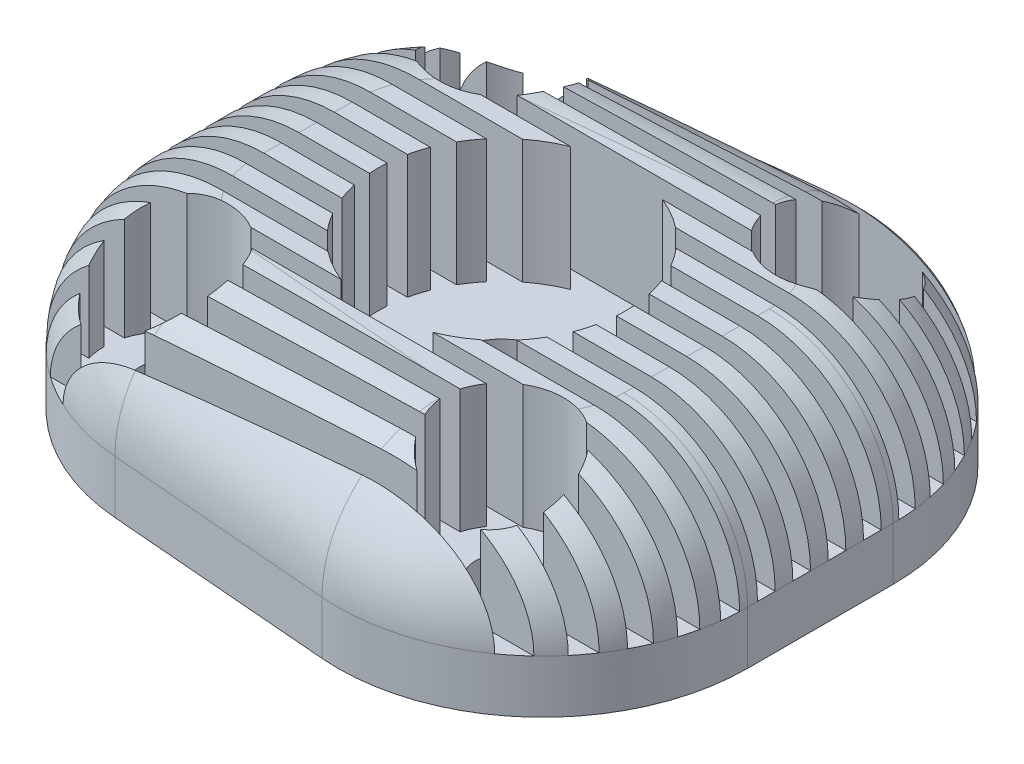
SolidWorks part; units mm, degrees
material "Alloy Steel"
ref_plane "Front Plane" through (0, 0, 0) normal (0, 0, 1) x (1, 0, 0)
ref_plane "Top Plane" through (0, 0, 0) normal (0, 1, 0) x (1, 0, 0)
ref_plane "Right Plane" through (0, 0, 0) normal (1, 0, 0) x (0, 0, -1)
sketch "Sketch1" plane through (0, 0, 0) normal (0, 1, 0) x (1, 0, 0)
  line L0 (5.2212, 15.708) -> (-7.5303, 14.4316)
  line L1 (-17.9681, 2.8969) -> (-17.9681, -3.0145)
  line L2 (-7.3192, -14.5684) -> (5.4324, -15.6096)
  line L3 (17.9681, -4.0557) -> (17.9681, 4.1733)
  line L4 (-17.9681, -0.0588) -> (17.9681, 0.0588) construction
  arc A0 (-7.5303, 14.4316) -> (-17.9681, 2.8969) centre (-6.3758, 2.8969) ccw
  arc A1 (-17.9681, -3.0145) -> (-7.3192, -14.5684) centre (-6.3758, -3.0145) ccw
  arc A2 (5.4324, -15.6096) -> (17.9681, -4.0557) centre (6.3758, -4.0557) ccw
  arc A3 (17.9681, 4.1733) -> (5.2212, 15.708) centre (6.3758, 4.1733) ccw
  point P14 (0, 0)
  dimension "D1" = 29
extrude "Boss-Extrude1" add sketch "Sketch1" along normal blind 10
sketch "Sketch3" plane through (0, 0, 0) normal (0, -1, 0) x (1, 0, 0)
  line L0 (-15.9681, 3.0145) -> (-15.9681, -2.8969)
  line L1 (-7.3311, -12.4416) -> (5.4204, -13.7179)
  line L2 (15.9681, -4.1733) -> (15.9681, 4.0557)
  line L3 (5.5951, 13.6162) -> (-7.1564, 12.575)
  line L4 (17.9681, -4.1733) -> (17.9681, 4.0557)
  line L5 (5.4324, 15.6096) -> (-7.3192, 14.5684)
  line L6 (-17.9681, 3.0145) -> (-17.9681, -2.8969)
  line L7 (-7.5303, -14.4316) -> (5.2212, -15.708)
  line L8 (17.9681, -4.1733) -> (17.9681, 4.0557) construction
  line L9 (5.4324, 15.6096) -> (-7.3192, 14.5684) construction
  line L10 (-17.9681, 3.0145) -> (-17.9681, -2.8969) construction
  line L11 (-7.5303, -14.4316) -> (5.2212, -15.708) construction
  arc A0 (-7.1564, 12.575) -> (-15.9681, 3.0145) centre (-6.3758, 3.0145) ccw
  arc A1 (-15.9681, -2.8969) -> (-7.3311, -12.4416) centre (-6.3758, -2.8969) ccw
  arc A2 (5.4204, -13.7179) -> (15.9681, -4.1733) centre (6.3758, -4.1733) ccw
  arc A3 (15.9681, 4.0557) -> (5.5951, 13.6162) centre (6.3758, 4.0557) ccw
  arc A4 (5.2212, -15.708) -> (17.9681, -4.1733) centre (6.3758, -4.1733) ccw
  arc A5 (17.9681, 4.0557) -> (5.4324, 15.6096) centre (6.3758, 4.0557) ccw
  arc A6 (-7.3192, 14.5684) -> (-17.9681, 3.0145) centre (-6.3758, 3.0145) ccw
  arc A7 (-17.9681, -2.8969) -> (-7.5303, -14.4316) centre (-6.3758, -2.8969) ccw
  arc A8 (5.2212, -15.708) -> (17.9681, -4.1733) centre (6.3758, -4.1733) ccw construction
  arc A9 (17.9681, 4.0557) -> (5.4324, 15.6096) centre (6.3758, 4.0557) ccw construction
  arc A10 (-7.3192, 14.5684) -> (-17.9681, 3.0145) centre (-6.3758, 3.0145) ccw construction
  arc A11 (-17.9681, -2.8969) -> (-7.5303, -14.4316) centre (-6.3758, -2.8969) ccw construction
  dimension "D1" = 0
  dimension "D2" = 2
extrude "Boss-Extrude2" add sketch "Sketch3" along normal blind 0.5
sketch "Sketch4" plane through (0, -0.5, 0) normal (0, -1, 0) x (1, 0, 0)
  circle A0 centre (0, 0) radius 10.5
  dimension "D1" = 21
extrude "Boss-Extrude3" add sketch "Sketch4" along normal blind 3.5
sketch "Sketch5" plane through (0, -4, 0) normal (0, -1, 0) x (1, 0, 0)
  circle A0 centre (0, 0) radius 3
  dimension "D1" = 6
sketch "Sketch7" plane through (0, 10, 0) normal (0, 1, 0) x (1, 0, 0)
  line L1 (9.5, -9.5) -> (-9.5, -9.5) construction
  line L2 (9.5, -9.5) -> (9.5, 9.5) construction
  line L3 (9.5, 9.5) -> (-9.5, 9.5) construction
  line L4 (-9.5, -9.5) -> (-9.5, 9.5) construction
  line L5 (9.5, -9.5) -> (-9.5, 9.5) construction
  line L6 (9.5, 9.5) -> (-9.5, -9.5) construction
  circle A0 centre (0, 0) radius 7
  dimension "D1" = 14
  dimension "D2" = 19
  dimension "D3" = 19
sketch "Sketch8" plane through (0, 10, 0) normal (0, 1, 0) x (1, 0, 0)
  line L1 (9.5, -9.5) -> (-9.5, -9.5) construction
  line L2 (9.5, -9.5) -> (9.5, 9.5) construction
  line L3 (9.5, 9.5) -> (-9.5, 9.5) construction
  line L4 (-9.5, -9.5) -> (-9.5, 9.5) construction
  circle A0 centre (-9.5, 9.5) radius 1.5
  circle A1 centre (9.5, 9.5) radius 1.5
  circle A2 centre (9.5, -9.5) radius 1.5
  circle A3 centre (-9.5, -9.5) radius 1.5
  dimension "D5" = 3
  dimension "D1" = 19
  dimension "D2" = 19
  dimension "D3" = 9.5
  dimension "D4" = 9.5
fillet "Fillet2" radius 7 8 edges at (-17.9681, 10, 0.0588) (-14.9713, 10, -10.675) (-1.1546, 10, -15.0698) (14.1539, 10, -12.7688) (17.9681, 10, -0.0588) (14.2322, 10, 12.5798) (-0.9434, 10, 15.089) (-14.8998, 10, 10.8709)
sketch "Sketch10" plane through (17.9681, 0, 0) normal (1, 0, 0) x (0, 0, -1)
  line L0 (-13.5, 3) -> (-13.5, 11)
  line L2 (-4.0557, 3) -> (-15.648, 3) construction
  line L3 (-13.5, 11) -> (-12.5, 11)
  line L4 (0, 0) -> (0, 15.1807) construction
  line L5 (-13.5, 3) -> (-12.5, 3)
  line L6 (-12.5, 3) -> (-12.5, 11)
  line L7 (-10.5, 3) -> (-10.5, 11)
  line L8 (-11.5, 3) -> (-11.5, 11)
  line L9 (-11.5, 11) -> (-10.5, 11)
  line L10 (-11.5, 3) -> (-10.5, 3)
  line L11 (-8.5, 3) -> (-8.5, 11)
  line L12 (-9.5, 3) -> (-9.5, 11)
  line L13 (-9.5, 11) -> (-8.5, 11)
  line L14 (-9.5, 3) -> (-8.5, 3)
  line L15 (-6.5, 3) -> (-6.5, 11)
  line L16 (-7.5, 3) -> (-7.5, 11)
  line L17 (-7.5, 11) -> (-6.5, 11)
  line L18 (-7.5, 3) -> (-6.5, 3)
  line L19 (-4.5, 3) -> (-4.5, 11)
  line L20 (-5.5, 3) -> (-5.5, 11)
  line L21 (-5.5, 11) -> (-4.5, 11)
  line L22 (-5.5, 3) -> (-4.5, 3)
  line L23 (-2.5, 3) -> (-2.5, 11)
  line L24 (-3.5, 3) -> (-3.5, 11)
  line L25 (-3.5, 11) -> (-2.5, 11)
  line L26 (-3.5, 3) -> (-2.5, 3)
  line L27 (-0.5, 3) -> (-0.5, 11)
  line L28 (-1.5, 3) -> (-1.5, 11)
  line L29 (-1.5, 11) -> (-0.5, 11)
  line L30 (-1.5, 3) -> (-0.5, 3)
  line L31 (1.5, 3) -> (1.5, 11)
  line L32 (0.5, 3) -> (0.5, 11)
  line L33 (0.5, 11) -> (1.5, 11)
  line L34 (0.5, 3) -> (1.5, 3)
  line L35 (3.5, 3) -> (3.5, 11)
  line L36 (2.5, 3) -> (2.5, 11)
  line L37 (2.5, 11) -> (3.5, 11)
  line L38 (2.5, 3) -> (3.5, 3)
  line L39 (5.5, 3) -> (5.5, 11)
  line L40 (4.5, 3) -> (4.5, 11)
  line L41 (4.5, 11) -> (5.5, 11)
  line L42 (4.5, 3) -> (5.5, 3)
  line L43 (7.5, 3) -> (7.5, 11)
  line L44 (6.5, 3) -> (6.5, 11)
  line L45 (6.5, 11) -> (7.5, 11)
  line L46 (6.5, 3) -> (7.5, 3)
  line L47 (9.5, 3) -> (9.5, 11)
  line L48 (8.5, 3) -> (8.5, 11)
  line L49 (8.5, 11) -> (9.5, 11)
  line L50 (8.5, 3) -> (9.5, 3)
  line L51 (11.5, 3) -> (11.5, 11)
  line L52 (10.5, 3) -> (10.5, 11)
  line L53 (10.5, 11) -> (11.5, 11)
  line L54 (10.5, 3) -> (11.5, 3)
  line L55 (13.5, 3) -> (13.5, 11)
  line L56 (12.5, 3) -> (12.5, 11)
  line L57 (12.5, 11) -> (13.5, 11)
  line L58 (12.5, 3) -> (13.5, 3)
  dimension "D1" = 13.5
  dimension "D2" = 12.5
  dimension "D3" = 8
  dimension "D5" = 1
  dimension "D4" = 14
extrude "Cut-Extrude12" cut sketch "Sketch10" against normal through all
extrude "Cut-Extrude13" cut sketch "Sketch5" against normal up to next
extrude "Cut-Extrude14" cut sketch "Sketch7" against normal blind 7
extrude "Cut-Extrude15" cut sketch "Sketch8" against normal through all
ref_plane "Plane1" through (0, 10, 0) normal (0, 1, 0) x (1, 0, 0)
sketch "Sketch14" plane through (0, 10, 0) normal (0, 1, 0) x (1, 0, 0)
  line L1 (9.5, -9.5) -> (-9.5, -9.5) construction
  line L2 (9.5, -9.5) -> (9.5, 9.5) construction
  line L3 (9.5, 9.5) -> (-9.5, 9.5) construction
  line L4 (-9.5, -9.5) -> (-9.5, 9.5) construction
  line L5 (9.5, -9.5) -> (-9.5, 9.5) construction
  line L6 (9.5, 9.5) -> (-9.5, -9.5) construction
  circle A0 centre (-9.5, 9.5) radius 3.5
  circle A1 centre (9.5, 9.5) radius 3.5
  circle A2 centre (9.5, -9.5) radius 3.5
  circle A3 centre (-9.5, -9.5) radius 3.5
  point P0 (0, 0)
  dimension "D1" = 7
extrude "Cut-Extrude17" cut sketch "Sketch14" against normal blind 7
sketch "Sketch15" plane through (0, -4, 0) normal (0, -1, 0) x (1, 0, 0)
  circle A0 centre (0, 0) radius 6.5
  dimension "D1" = 13
extrude "Cut-Extrude18" cut sketch "Sketch15" against normal blind 3.5
fillet "Fillet3" radius 3.5 1 edges at (0, -0.5, -6.5)
